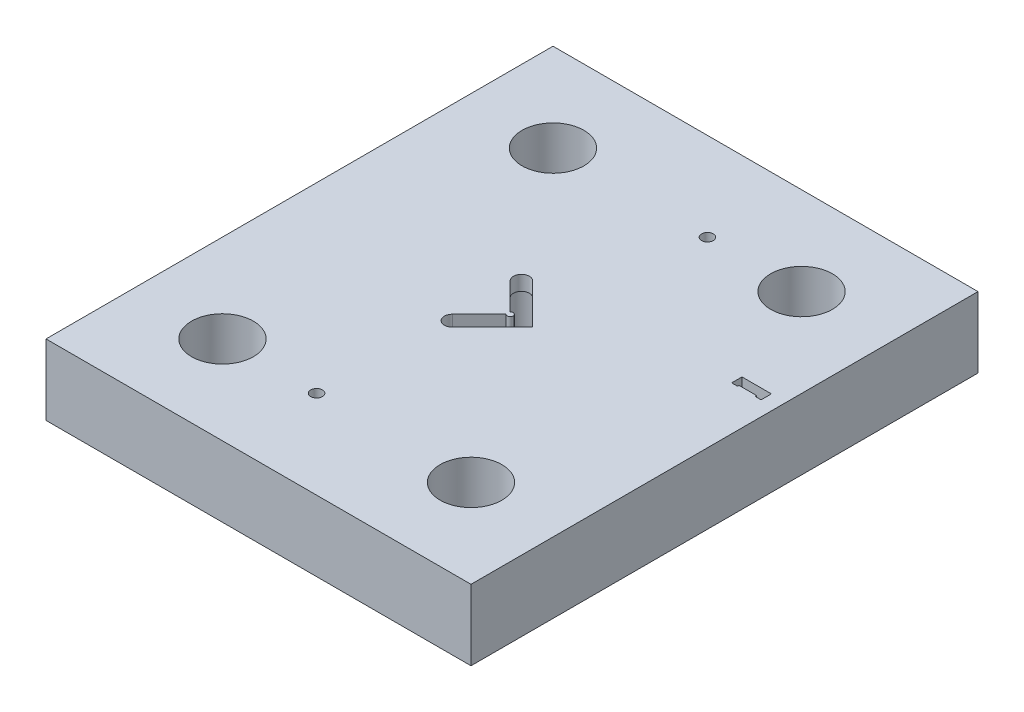
SolidWorks part; units mm, degrees
ref_plane "Front Plane" through (0, 0, 0) normal (0, 0, 1) x (1, 0, 0)
ref_plane "Top Plane" through (0, 0, 0) normal (0, 1, 0) x (1, 0, 0)
ref_plane "Right Plane" through (0, 0, 0) normal (1, 0, 0) x (0, 0, -1)
sketch "Sketch1" plane through (0, 0, 0) normal (0, 1, 0) x (1, 0, 0)
  line L1 (-72.25, -86.19) -> (72.25, -86.19)
  line L2 (-72.25, -86.19) -> (-72.25, 86.19)
  line L3 (-72.25, 86.19) -> (72.25, 86.19)
  line L4 (72.25, -86.19) -> (72.25, 86.19)
  line L5 (-72.25, -86.19) -> (72.25, 86.19) construction
  line L6 (-72.25, 86.19) -> (72.25, -86.19) construction
  point P0 (0, 0)
  dimension "D1" = 144.5
  dimension "D2" = 172.38
extrude "Boss-Extrude1" add sketch "Sketch1" along normal blind 24
sketch "Sketch2" plane through (0, 24, 0) normal (0, 1, 0) x (1, 0, 0)
  line L0 (-72.25, 86.19) -> (-72.25, -86.19) construction
  line L1 (-72.25, -17.44) -> (72.25, -17.44) construction
  line L2 (-72.25, -17.44) -> (-72.25, 17.94) construction
  line L3 (-72.25, 17.94) -> (57.25, 17.94) construction
  line L4 (72.25, -17.44) -> (72.25, 19.6447) construction
  line L5 (72.25, -86.19) -> (72.25, 86.19) construction
  line L6 (62.25, 17.94) -> (62.25, 23.33) construction
  line L8 (57.25, 17.94) -> (57.25, 20.94) construction
  line L9 (57.25, 20.94) -> (72.25, 20.94) construction
  line L10 (72.25, 19.6447) -> (72.25, 20.94) construction
  line L11 (57.25, 17.44) -> (59.25, 17.44)
  line L12 (57.25, 17.44) -> (57.25, 20.94)
  line L13 (57.25, 20.94) -> (67.25, 20.94)
  line L14 (67.25, 17.44) -> (67.25, 20.94)
  line L16 (59.25, 17.44) -> (59.25, 17.94)
  line L17 (59.25, 17.94) -> (65.25, 17.94)
  line L18 (65.25, 17.44) -> (65.25, 17.94)
  line L19 (65.25, 17.44) -> (67.25, 17.44)
  line L20 (0, 0) -> (-1.2535, 0) construction
  line L21 (-10.4555, 9.8288) -> (-1.3339, 0.7071)
  line L22 (-1.3339, -0.7071) -> (-10.4555, -9.8288)
  line L23 (-6.6372, 13.6472) -> (7.01, 0)
  line L24 (7.01, 0) -> (-6.6372, -13.6472)
  line L25 (72.25, 86.19) -> (-72.25, 86.19) construction
  line L26 (-0.6268, 0) -> (-10.4555, -9.8288) construction
  line L27 (-10.4555, 9.8288) -> (-0.6268, 0) construction
  line L28 (0, 0) -> (0, 4.866) construction
  line L30 (-5.7865, 0) -> (0, 0) construction
  line L32 (-72.25, -86.19) -> (72.25, -86.19) construction
  arc A0 (-10.4555, 9.8288) -> (-6.6372, 13.6472) centre (-8.5463, 11.738) cw
  arc A1 (-6.6372, -13.6472) -> (-10.4555, -9.8288) centre (-8.5463, -11.738) cw
  arc A2 (-1.3339, -0.7071) -> (-1.3339, 0.7071) centre (-0.6268, 0) ccw
  circle A3 centre (42.25, 56.19) radius 10.5
  circle A4 centre (-42.25, 56.19) radius 10.5
  circle A5 centre (-42.25, -56.19) radius 10.5
  circle A6 centre (42.25, -56.19) radius 10.5
  circle A7 centre (10.25, 56.19) radius 1.99
  circle A8 centre (-10.25, -56.19) radius 1.99
  point P34 (7.01, 0)
  dimension "D10" = 2
  dimension "D14" = 21
  dimension "D21" = 3.98
  dimension "D22" = 3.98
  dimension "D1" = 10
  dimension "D2" = 6
  dimension "D3" = 0.5
  dimension "D4" = 3.5
  dimension "D5" = 0.5
  dimension "D6" = 15
  dimension "D8" = 19.3
  dimension "D9" = 19.3
  dimension "D11" = 17.94
  dimension "D12" = 17.44
  dimension "D13" = 50.24
  dimension "D15" = 30
  dimension "D16" = 30
  dimension "D17" = 62
  dimension "D18" = 62
  dimension "D19" = 30
  dimension "D20" = 30
  dimension "D7" = 5.4
extrude "Cut-Extrude1" cut sketch "Sketch2" against normal blind 80
sketch "Sketch4" plane through (0, 0, 0) normal (0, -1, 0) x (1, 0, 0)
  line L5 (-4.5017, -15.7826) -> (11.2526, -0.0283)
  line L6 (-4.8128, -0.0283) -> (-12.5344, -7.7499)
  line L7 (-12.5344, 7.6933) -> (-4.8128, -0.0283)
  line L8 (11.2526, -0.0283) -> (-4.5017, 15.7261)
  line L9 (-4.5017, -15.7826) -> (11.2526, -0.0283)
  line L10 (-4.8128, -0.0283) -> (-12.5344, -7.7499)
  line L11 (-12.5344, 7.6933) -> (-4.8128, -0.0283)
  line L12 (11.2526, -0.0283) -> (-4.5017, 15.7261)
  arc A2 (-12.5344, -7.7499) -> (-4.5017, -15.7826) centre (-8.5181, -11.7663) ccw
  arc A3 (-4.5017, 15.7261) -> (-12.5344, 7.6933) centre (-8.5181, 11.7097) ccw
  arc A4 (-12.5344, -7.7499) -> (-4.5017, -15.7826) centre (-8.5181, -11.7663) ccw
  arc A5 (-4.5017, 15.7261) -> (-12.5344, 7.6933) centre (-8.5181, 11.7097) ccw
  dimension "D1" = 0
extrude "Cut-Extrude3" cut sketch "Sketch4" against normal blind 19
